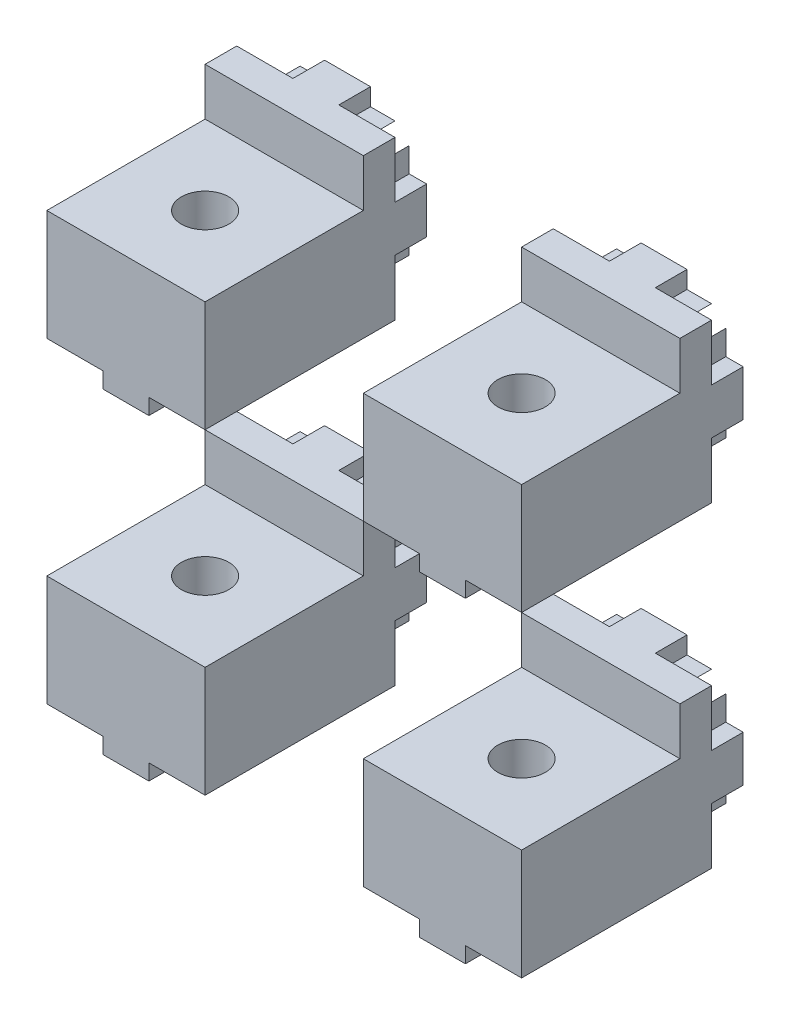
SolidWorks part; units mm, degrees
ref_plane "Front Plane" through (0, 0, 0) normal (0, 0, 1) x (1, 0, 0)
ref_plane "Top Plane" through (0, 0, 0) normal (0, 1, 0) x (1, 0, 0)
ref_plane "Right Plane" through (0, 0, 0) normal (1, 0, 0) x (0, 0, -1)
ref_axis "Axis1" through (0, 0, -1.2) along (0, 0, 1)
sketch "Sketch1" plane through (0, 0, 0) normal (0, 0, 1) x (1, 0, 0)
  line L1 (-5, -5) -> (5, -5)
  line L2 (-5, -5) -> (-5, 5)
  line L3 (-5, 5) -> (5, 5)
  line L4 (5, -5) -> (5, 5)
  line L5 (-5, -5) -> (5, 5) construction
  line L6 (-5, 5) -> (5, -5) construction
  point P0 (0, 0)
  dimension "D1" = 10
  dimension "D2" = 10
extrude "Main" add sketch "Sketch1" along normal blind 12
sketch "Sketch2" plane through (0, 0, 0) normal (0, 0, -1) x (-1, 0, 0)
  line L0 (-5, 1.45) -> (-3.9, 1.45)
  line L1 (-5, -5) -> (-5, 5) construction
  line L2 (-3.9, 1.45) -> (-3.9, 3)
  line L3 (-3.9, -1.45) -> (-5, -1.45)
  line L4 (-5, 1.45) -> (-5, -1.45)
  line L5 (-3.9, 3) -> (-2.1, 0.95)
  line L6 (-2.1, 0.95) -> (-2.1, -0.95)
  line L7 (-2.1, -0.95) -> (-3.9, -3)
  line L8 (-3.9, -3) -> (-3.9, -1.45)
  line L9 (-5, 5) -> (5, 5) construction
  point P5 (-2.1, 0)
  dimension "D1" = 2.9
  dimension "D2" = 1.1
  dimension "D3" = 1.9
  dimension "D4" = 2.1
  dimension "D5" = 2
extrude "AntiRotationSystem" add sketch "Sketch2" along normal blind 2
pattern_circular "CirPattern1" count 4 over 360 about axis through (0, 0, -1.2) along (0, 0, 1) of "AntiRotationSystem"
sketch "Sketch3" plane through (0, 5, 0) normal (0, 1, 0) x (1, 0, 0)
  line L0 (-5, -12) -> (-5, 0) construction
  line L1 (5, -12) -> (-5, -12)
  line L2 (5, -12) -> (5, -2)
  line L3 (5, -2) -> (-5, -2)
  line L4 (-5, -12) -> (-5, -2)
  dimension "D1" = 10
extrude "MakerBeamSquareHoleForScrew" cut sketch "Sketch3" against normal blind 3
sketch "Sketch5" plane through (0, -5, 0) normal (0, -1, 0) x (-1, 0, 0)
  line L0 (5, -12) -> (-5, -12) construction
  line L1 (1.45, 0) -> (-1.45, 0)
  line L2 (1.45, 0) -> (1.45, -12)
  line L3 (1.45, -12) -> (-1.45, -12)
  line L4 (-1.45, 0) -> (-1.45, -12)
  line L5 (0, 1.2) -> (0, -3.2) construction
  line L6 (-1.45, 0) -> (-5, 0) construction
  point P6 (0, -12)
  dimension "D1" = 2.9
extrude "MakerBeamRail" add sketch "Sketch5" along normal blind 1
sketch "Sketch4" plane through (0, 2, 0) normal (0, 1, 0) x (1, 0, 0)
  line L0 (-5, -12) -> (5, -12) construction
  line L1 (0, 1.2) -> (0, -3.2) construction
  circle A0 centre (0, -7) radius 1.5
  dimension "D1" = 3
  dimension "D2" = 5
extrude "VerticalMakerBeamHole" cut sketch "Sketch4" against normal through all
pattern_linear "LPattern1" count 2 spacing 20 along (-1, 0, 0) count 2 spacing 20 along (0, -1, 0) of bodies 115
